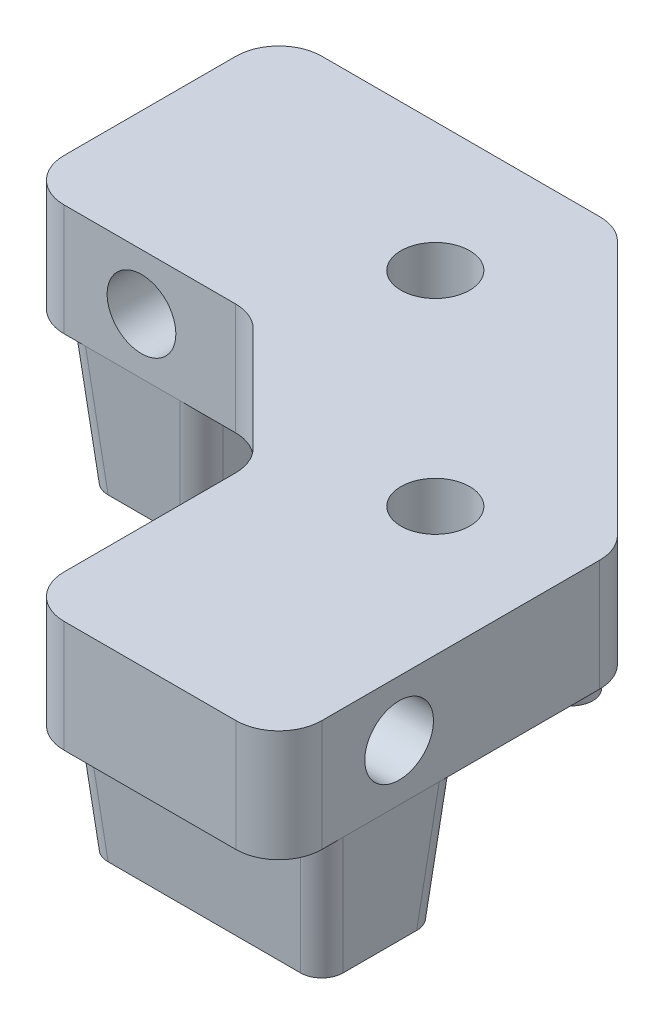
SolidWorks part; units mm, degrees
ref_plane "Front Plane" through (0, 0, 0) normal (0, 0, 1) x (1, 0, 0)
ref_plane "Top Plane" through (0, 0, 0) normal (0, 1, 0) x (1, 0, 0)
ref_plane "Right Plane" through (0, 0, 0) normal (1, 0, 0) x (0, 0, -1)
sketch "Sketch1" plane through (0, 0, 0) normal (0, 1, 0) x (1, 0, 0)
  line L1 (0, -15) -> (-15, 0)
  line L2 (0, -42) -> (30, -42)
  line L3 (-2.5736, 30) -> (30, -2.5736)
  line L4 (-42, 0) -> (-42, 30)
  line L5 (30, -2.5736) -> (30, -42)
  line L6 (-15, 0) -> (-42, 0)
  line L7 (0, -42) -> (0, -15)
  line L8 (-42, 30) -> (-2.5736, 30)
  circle A0 centre (-8.7868, 15) radius 4
  circle A1 centre (15, -8.7868) radius 4
extrude "Extrude1" add sketch "Sketch1" along normal blind 13
fillet "Fillet5" radius 5 8 edges at (0, 6.5, 42) (30, 6.5, 42) (30, 6.5, 2.5736) (-2.5736, 6.5, -30) (-42, 6.5, -30) (-42, 6.5, 0) (-15, 6.5, 0) (0, 6.5, 15)
sketch "Sketch5" plane through (-7.5, 0, 7.5) normal (-0.7071, 0, 0.7071) x (0.7071, 0, 0.7071)
  circle A0 centre (0, 6.5) radius 4
extrude "Extrude5" cut sketch "Sketch5" against normal blind 30
sketch "Sketch6" plane through (0, 0, 0) normal (0, 0, 1) x (1, 0, 0)
  circle A0 centre (-28, 6.5) radius 4
extrude "Extrude6" cut sketch "Sketch6" against normal blind 30
sketch "Sketch8" plane through (0, 0, 0) normal (-1, 0, 0) x (0, 0, 1)
  circle A0 centre (28, 6.5) radius 4
extrude "Extrude7" cut sketch "Sketch8" against normal blind 30
sketch "Sketch9" plane through (0, 0, 0) normal (0, -1, 0) x (1, 0, 0)
  line L0 (-37, -30) -> (-37, 0)
  line L3 (-37, 0) -> (-21, 0)
  line L5 (-37, 0) -> (-17.0711, 0) construction
  line L7 (-37, -30) -> (-21, -30)
  line L8 (18.663, -8.7635) -> (8.7635, -18.663)
  line L9 (-13.5355, 1.4645) -> (-1.4645, 13.5355) construction
  line L10 (28.5355, 1.1091) -> (-1.1091, -28.5355) construction
  line L11 (30, 37) -> (0, 37)
  line L12 (18.663, -8.7635) -> (-2.5503, 12.4497)
  line L13 (-2.5503, 12.4497) -> (-12.4497, 2.5503)
  line L14 (-12.4497, 2.5503) -> (8.7635, -18.663)
  line L15 (0, 37) -> (0, 21)
  line L16 (0, 17.0711) -> (0, 37) construction
  line L17 (30, 37) -> (30, 20.8223)
  line L19 (30, 37) -> (30, 4.6447) construction
  line L21 (-4.6447, -30) -> (-37, -30) construction
  line L22 (-21, -30) -> (-21, 0)
  line L23 (0, 21) -> (30, 20.8223)
extrude "Extrude8" add sketch "Sketch9" along normal blind 15 draft 5
fillet "Fillet8" radius 2.5 12 edges at (-11.5218, -7.5, 2.5503) (-2.5503, -7.5, 11.5218) (0.6562, -7.5, 21.6523) (0.6562, -7.5, 36.3438) (-36.3438, -7.5, -0.6562) (-36.3438, -7.5, -29.3438) (8.7635, -7.5, -17.735) (29.3438, -7.5, 36.3438) (29.3438, -7.5, 21.4824) (17.735, -7.5, -8.7635)
